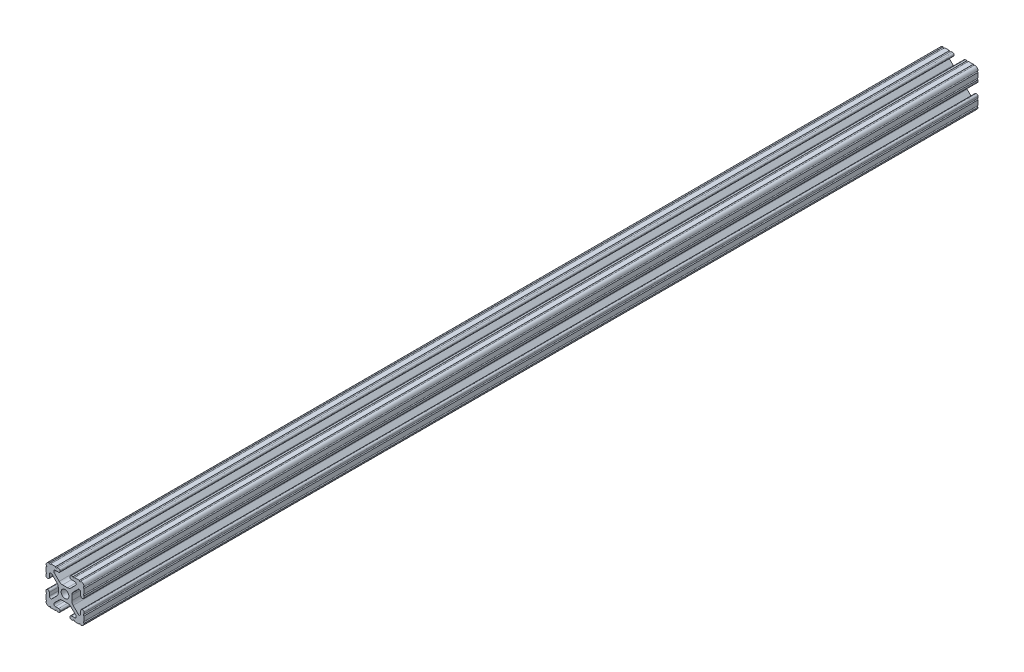
SolidWorks part; units mm, degrees
material "6061 Alloy"
ref_plane "Front" through (0, 0, 0) normal (0, 0, 1) x (1, 0, 0)
ref_plane "Top" through (0, 0, 0) normal (0, 1, 0) x (1, 0, 0)
ref_plane "Right" through (0, 0, 0) normal (1, 0, 0) x (0, 0, -1)
sketch "Sketch1" plane through (0, 0, 0) normal (0, 0, 1) x (1, 0, 0)
  line L0 (-3.2512, 12.7) -> (-3.2512, -12.7) construction
  line L1 (-12.7, -12.7) -> (12.7, -12.7) construction
  line L2 (-12.7, -12.7) -> (-12.7, 12.7) construction
  line L3 (-12.7, 12.7) -> (12.7, 12.7) construction
  line L4 (12.7, -12.7) -> (12.7, 12.7) construction
  line L5 (0, 12.7) -> (0, -12.7) construction
  line L6 (-12.7, 0) -> (12.7, 0) construction
  line L7 (3.2512, 12.7) -> (3.2512, -12.7) construction
  line L8 (-3.2512, 12.7) -> (3.2512, -12.7) construction
  circle A0 centre (0, 0) radius 2.6035
  point P0 (0, 0)
  line B0 (-7.5107, 9.4563) -> (7.5107, 9.4563) construction
  line B1 (-7.4968, -9.4098) -> (7.4968, -9.4098) construction
  line B2 (-7.1797, -8.6452) -> (-3.9523, -5.4237)
  line B3 (-1.7093, -4.4958) -> (1.7093, -4.4958)
  line B4 (3.9523, -5.4237) -> (7.1797, -8.6452)
  line B5 (6.4164, -10.4902) -> (4.2875, -10.4902)
  line B6 (3.2385, -11.5392) -> (3.2385, -11.651)
  line B7 (4.2875, -12.7) -> (5.3171, -12.7)
  line B8 (6.3331, -12.7) -> (9.5504, -12.7)
  line B9 (12.7, -9.5504) -> (12.7, -6.3331)
  line B10 (12.7, -5.3171) -> (12.7, -4.2875)
  line B11 (11.651, -3.2385) -> (11.5392, -3.2385)
  line B12 (10.4902, -4.2875) -> (10.4902, -6.4021)
  line B13 (8.7371, -7.1294) -> (5.441, -3.8408)
  line B14 (4.5085, -1.5932) -> (4.5085, 1.5932)
  line B15 (5.441, 3.8408) -> (8.7371, 7.1294)
  line B16 (10.4902, 6.4021) -> (10.4902, 4.2875)
  line B17 (11.5392, 3.2385) -> (11.651, 3.2385)
  line B18 (12.7, 4.2875) -> (12.7, 5.3171)
  line B19 (12.7, 6.3331) -> (12.7, 9.5504)
  line B20 (9.5504, 12.7) -> (6.3331, 12.7)
  line B21 (5.3171, 12.7) -> (4.2875, 12.7)
  line B22 (3.2385, 11.651) -> (3.2385, 11.5392)
  line B23 (4.2875, 10.4902) -> (6.4768, 10.4902)
  line B24 (7.207, 8.7244) -> (3.8983, 5.4232)
  line B25 (1.6558, 4.4958) -> (-1.6558, 4.4958)
  line B26 (-3.8983, 5.4232) -> (-7.207, 8.7244)
  line B27 (-6.4768, 10.4902) -> (-4.2875, 10.4902)
  line B28 (-3.2385, 11.5392) -> (-3.2385, 11.651)
  line B29 (-4.2875, 12.7) -> (-5.3171, 12.7)
  line B30 (-6.3331, 12.7) -> (-9.5504, 12.7)
  line B31 (-12.7, 9.5504) -> (-12.7, 6.3331)
  line B32 (-12.7, 5.3171) -> (-12.7, 4.2875)
  line B33 (-11.651, 3.2385) -> (-11.5392, 3.2385)
  line B34 (-10.4902, 4.2875) -> (-10.4902, 6.4021)
  line B35 (-8.7371, 7.1294) -> (-5.441, 3.8408)
  line B36 (-4.5085, 1.5932) -> (-4.5085, -1.5932)
  line B37 (-5.441, -3.8408) -> (-8.7371, -7.1294)
  line B38 (-10.4902, -6.4021) -> (-10.4902, -4.2875)
  line B39 (-11.5392, -3.2385) -> (-11.651, -3.2385)
  line B40 (-12.7, -4.2875) -> (-12.7, -5.3171)
  line B41 (-12.7, -6.3331) -> (-12.7, -9.5504)
  line B42 (-9.5504, -12.7) -> (-6.3331, -12.7)
  line B43 (-5.3171, -12.7) -> (-4.2875, -12.7)
  line B44 (-3.2385, -11.651) -> (-3.2385, -11.5392)
  line B45 (-4.2875, -10.4902) -> (-6.4164, -10.4902)
  circle B46 centre (0, 0) radius 2.6035
  arc B47 (-7.1797, -8.6452) -> (-6.4164, -10.4902) centre (-6.4164, -9.4098) ccw
  arc B48 (-1.7093, -4.4958) -> (-3.9523, -5.4237) centre (-1.7093, -7.6708) ccw
  arc B49 (3.9523, -5.4237) -> (1.7093, -4.4958) centre (1.7093, -7.6708) ccw
  arc B50 (6.4164, -10.4902) -> (7.1797, -8.6452) centre (6.4164, -9.4098) ccw
  arc B51 (4.2875, -10.4902) -> (3.2385, -11.5392) centre (4.2875, -11.5392) ccw
  arc B52 (3.2385, -11.651) -> (4.2875, -12.7) centre (4.2875, -11.651) ccw
  arc B53 (6.3331, -12.7) -> (5.3171, -12.7) centre (5.8251, -12.7) ccw
  arc B54 (10.5664, -12.6998) -> (9.5504, -12.7) centre (10.0584, -12.7) ccw
  arc B55 (10.5664, -12.6998) -> (12.6998, -10.5664) centre (10.5918, -10.5918) ccw
  arc B56 (12.7, -9.5504) -> (12.6998, -10.5664) centre (12.7, -10.0584) ccw
  arc B57 (12.7, -5.3171) -> (12.7, -6.3331) centre (12.7, -5.8251) ccw
  arc B58 (12.7, -4.2875) -> (11.651, -3.2385) centre (11.651, -4.2875) ccw
  arc B59 (11.5392, -3.2385) -> (10.4902, -4.2875) centre (11.5392, -4.2875) ccw
  arc B60 (8.7371, -7.1294) -> (10.4902, -6.4021) centre (9.4628, -6.4021) ccw
  arc B61 (4.5085, -1.5932) -> (5.441, -3.8408) centre (7.6835, -1.5932) ccw
  arc B62 (5.441, 3.8408) -> (4.5085, 1.5932) centre (7.6835, 1.5932) ccw
  arc B63 (10.4902, 6.4021) -> (8.7371, 7.1294) centre (9.4628, 6.4021) ccw
  arc B64 (10.4902, 4.2875) -> (11.5392, 3.2385) centre (11.5392, 4.2875) ccw
  arc B65 (11.651, 3.2385) -> (12.7, 4.2875) centre (11.651, 4.2875) ccw
  arc B66 (12.7, 6.3331) -> (12.7, 5.3171) centre (12.7, 5.8251) ccw
  arc B67 (12.6998, 10.5664) -> (12.7, 9.5504) centre (12.7, 10.0584) ccw
  arc B68 (12.6998, 10.5664) -> (10.5664, 12.6998) centre (10.5918, 10.5918) ccw
  arc B69 (9.5504, 12.7) -> (10.5664, 12.6998) centre (10.0584, 12.7) ccw
  arc B70 (5.3171, 12.7) -> (6.3331, 12.7) centre (5.8251, 12.7) ccw
  arc B71 (4.2875, 12.7) -> (3.2385, 11.651) centre (4.2875, 11.651) ccw
  arc B72 (3.2385, 11.5392) -> (4.2875, 10.4902) centre (4.2875, 11.5392) ccw
  arc B73 (7.207, 8.7244) -> (6.4768, 10.4902) centre (6.4768, 9.4563) ccw
  arc B74 (1.6558, 4.4958) -> (3.8983, 5.4232) centre (1.6558, 7.6708) ccw
  arc B75 (-3.8983, 5.4232) -> (-1.6558, 4.4958) centre (-1.6558, 7.6708) ccw
  arc B76 (-6.4768, 10.4902) -> (-7.207, 8.7244) centre (-6.4768, 9.4563) ccw
  arc B77 (-4.2875, 10.4902) -> (-3.2385, 11.5392) centre (-4.2875, 11.5392) ccw
  arc B78 (-3.2385, 11.651) -> (-4.2875, 12.7) centre (-4.2875, 11.651) ccw
  arc B79 (-6.3331, 12.7) -> (-5.3171, 12.7) centre (-5.8251, 12.7) ccw
  arc B80 (-10.5664, 12.6998) -> (-9.5504, 12.7) centre (-10.0584, 12.7) ccw
  arc B81 (-10.5664, 12.6998) -> (-12.6998, 10.5664) centre (-10.5918, 10.5918) ccw
  arc B82 (-12.7, 9.5504) -> (-12.6998, 10.5664) centre (-12.7, 10.0584) ccw
  arc B83 (-12.7, 5.3171) -> (-12.7, 6.3331) centre (-12.7, 5.8251) ccw
  arc B84 (-12.7, 4.2875) -> (-11.651, 3.2385) centre (-11.651, 4.2875) ccw
  arc B85 (-11.5392, 3.2385) -> (-10.4902, 4.2875) centre (-11.5392, 4.2875) ccw
  arc B86 (-8.7371, 7.1294) -> (-10.4902, 6.4021) centre (-9.4628, 6.4021) ccw
  arc B87 (-4.5085, 1.5932) -> (-5.441, 3.8408) centre (-7.6835, 1.5932) ccw
  arc B88 (-5.441, -3.8408) -> (-4.5085, -1.5932) centre (-7.6835, -1.5932) ccw
  arc B89 (-10.4902, -6.4021) -> (-8.7371, -7.1294) centre (-9.4628, -6.4021) ccw
  arc B90 (-10.4902, -4.2875) -> (-11.5392, -3.2385) centre (-11.5392, -4.2875) ccw
  arc B91 (-11.651, -3.2385) -> (-12.7, -4.2875) centre (-11.651, -4.2875) ccw
  arc B92 (-12.7, -6.3331) -> (-12.7, -5.3171) centre (-12.7, -5.8251) ccw
  arc B93 (-12.6998, -10.5664) -> (-12.7, -9.5504) centre (-12.7, -10.0584) ccw
  arc B94 (-12.6998, -10.5664) -> (-10.5664, -12.6998) centre (-10.5918, -10.5918) ccw
  arc B95 (-9.5504, -12.7) -> (-10.5664, -12.6998) centre (-10.0584, -12.7) ccw
  arc B96 (-5.3171, -12.7) -> (-6.3331, -12.7) centre (-5.8251, -12.7) ccw
  arc B97 (-4.2875, -12.7) -> (-3.2385, -11.651) centre (-4.2875, -11.651) ccw
  arc B98 (-3.2385, -11.5392) -> (-4.2875, -10.4902) centre (-4.2875, -11.5392) ccw
  dimension "Center Hole Diameter" = 5.207
  dimension "Rail Width" = 25.4
  dimension "Rail Height" = 25.4
  dimension "T-Slot Width" = 6.5024
sketch_block_instance "Block1-1"
sketch_block "Block1"
sketch "Sketch2" plane through (0, 0, 0) normal (1, 0, 0) x (0, 0, -1)
  line L0 (-298.45, 0) -> (298.45, 0) construction
  line L1 (0, 0) -> (0, 12.7) construction
  line L2 (12.7, 12.7) -> (-12.7, 12.7) construction
  line L3 (-3048, -12.7) -> (3048, -12.7) construction
  line L4 (-179.07, 0) -> (0, 12.7) construction
  line L5 (0, 12.7) -> (179.07, 0) construction
  point P5 (-179.07, 0)
  point P9 (0, 12.7)
  point P12 (179.07, 0)
  dimension "Length Range [Min]" = 25.4
  dimension "Rep Length" = 596.9
  dimension "Length Range [Max]" = 6096
  dimension "D1" = 358.14
sketch "Sketch3" plane through (0, 0, 0) normal (0, 0, 1) x (1, 0, 0)
  line L0 (-7.1797, -8.6452) -> (-3.9523, -5.4237) construction
  line L1 (-4.2875, -10.4902) -> (-6.4164, -10.4902) construction
  line L2 (-3.2385, -11.651) -> (-3.2385, -11.5392) construction
  line L3 (-5.3171, -12.7) -> (-4.2875, -12.7) construction
  line L4 (-9.5504, -12.7) -> (-6.3331, -12.7) construction
  line L5 (-12.7, -6.3331) -> (-12.7, -9.5504) construction
  line L6 (-12.7, -4.2875) -> (-12.7, -5.3171) construction
  line L7 (-11.5392, -3.2385) -> (-11.651, -3.2385) construction
  line L8 (-10.4902, -6.4021) -> (-10.4902, -4.2875) construction
  line L9 (-5.441, -3.8408) -> (-8.7371, -7.1294) construction
  line L10 (-4.5085, 1.5932) -> (-4.5085, -1.5932) construction
  line L11 (-8.7371, 7.1294) -> (-5.441, 3.8408) construction
  line L12 (-10.4902, 4.2875) -> (-10.4902, 6.4021) construction
  line L13 (-11.651, 3.2385) -> (-11.5392, 3.2385) construction
  line L14 (-12.7, 5.3171) -> (-12.7, 4.2875) construction
  line L15 (-12.7, 9.5504) -> (-12.7, 6.3331) construction
  line L16 (-6.3331, 12.7) -> (-9.5504, 12.7) construction
  line L17 (-4.2875, 12.7) -> (-5.3171, 12.7) construction
  line L18 (-3.2385, 11.5392) -> (-3.2385, 11.651) construction
  line L19 (-6.4768, 10.4902) -> (-4.2875, 10.4902) construction
  line L20 (-3.8983, 5.4232) -> (-7.207, 8.7244) construction
  line L21 (1.6558, 4.4958) -> (-1.6558, 4.4958) construction
  line L22 (7.207, 8.7244) -> (3.8983, 5.4232) construction
  line L23 (4.2875, 10.4902) -> (6.4768, 10.4902) construction
  line L24 (3.2385, 11.651) -> (3.2385, 11.5392) construction
  line L25 (5.3171, 12.7) -> (4.2875, 12.7) construction
  line L26 (9.5504, 12.7) -> (6.3331, 12.7) construction
  line L27 (12.7, 6.3331) -> (12.7, 9.5504) construction
  line L28 (12.7, 4.2875) -> (12.7, 5.3171) construction
  line L29 (11.5392, 3.2385) -> (11.651, 3.2385) construction
  line L30 (10.4902, 6.4021) -> (10.4902, 4.2875) construction
  line L31 (5.441, 3.8408) -> (8.7371, 7.1294) construction
  line L32 (4.5085, -1.5932) -> (4.5085, 1.5932) construction
  line L33 (8.7371, -7.1294) -> (5.441, -3.8408) construction
  line L34 (10.4902, -4.2875) -> (10.4902, -6.4021) construction
  line L35 (11.651, -3.2385) -> (11.5392, -3.2385) construction
  line L36 (12.7, -5.3171) -> (12.7, -4.2875) construction
  line L37 (12.7, -9.5504) -> (12.7, -6.3331) construction
  line L38 (6.3331, -12.7) -> (9.5504, -12.7) construction
  line L39 (4.2875, -12.7) -> (5.3171, -12.7) construction
  line L40 (3.2385, -11.5392) -> (3.2385, -11.651) construction
  line L41 (6.4164, -10.4902) -> (4.2875, -10.4902) construction
  line L42 (3.9523, -5.4237) -> (7.1797, -8.6452) construction
  line L43 (-1.7093, -4.4958) -> (1.7093, -4.4958) construction
  line L44 (-7.1797, -8.6452) -> (-3.9523, -5.4237)
  line L45 (-4.2875, -10.4902) -> (-6.4164, -10.4902)
  line L46 (-3.2385, -11.651) -> (-3.2385, -11.5392)
  line L47 (-5.3171, -12.7) -> (-4.2875, -12.7)
  line L48 (-9.5504, -12.7) -> (-6.3331, -12.7)
  line L49 (-12.7, -6.3331) -> (-12.7, -9.5504)
  line L50 (-12.7, -4.2875) -> (-12.7, -5.3171)
  line L51 (-11.5392, -3.2385) -> (-11.651, -3.2385)
  line L52 (-10.4902, -6.4021) -> (-10.4902, -4.2875)
  line L53 (-5.441, -3.8408) -> (-8.7371, -7.1294)
  line L54 (-4.5085, 1.5932) -> (-4.5085, -1.5932)
  line L55 (-8.7371, 7.1294) -> (-5.441, 3.8408)
  line L56 (-10.4902, 4.2875) -> (-10.4902, 6.4021)
  line L57 (-11.651, 3.2385) -> (-11.5392, 3.2385)
  line L58 (-12.7, 5.3171) -> (-12.7, 4.2875)
  line L59 (-12.7, 9.5504) -> (-12.7, 6.3331)
  line L60 (-6.3331, 12.7) -> (-9.5504, 12.7)
  line L61 (-4.2875, 12.7) -> (-5.3171, 12.7)
  line L62 (-3.2385, 11.5392) -> (-3.2385, 11.651)
  line L63 (-6.4768, 10.4902) -> (-4.2875, 10.4902)
  line L64 (-3.8983, 5.4232) -> (-7.207, 8.7244)
  line L65 (1.6558, 4.4958) -> (-1.6558, 4.4958)
  line L66 (7.207, 8.7244) -> (3.8983, 5.4232)
  line L67 (4.2875, 10.4902) -> (6.4768, 10.4902)
  line L68 (3.2385, 11.651) -> (3.2385, 11.5392)
  line L69 (5.3171, 12.7) -> (4.2875, 12.7)
  line L70 (9.5504, 12.7) -> (6.3331, 12.7)
  line L71 (12.7, 6.3331) -> (12.7, 9.5504)
  line L72 (12.7, 4.2875) -> (12.7, 5.3171)
  line L73 (11.5392, 3.2385) -> (11.651, 3.2385)
  line L74 (10.4902, 6.4021) -> (10.4902, 4.2875)
  line L75 (5.441, 3.8408) -> (8.7371, 7.1294)
  line L76 (4.5085, -1.5932) -> (4.5085, 1.5932)
  line L77 (8.7371, -7.1294) -> (5.441, -3.8408)
  line L78 (10.4902, -4.2875) -> (10.4902, -6.4021)
  line L79 (11.651, -3.2385) -> (11.5392, -3.2385)
  line L80 (12.7, -5.3171) -> (12.7, -4.2875)
  line L81 (12.7, -9.5504) -> (12.7, -6.3331)
  line L82 (6.3331, -12.7) -> (9.5504, -12.7)
  line L83 (4.2875, -12.7) -> (5.3171, -12.7)
  line L84 (3.2385, -11.5392) -> (3.2385, -11.651)
  line L85 (6.4164, -10.4902) -> (4.2875, -10.4902)
  line L86 (3.9523, -5.4237) -> (7.1797, -8.6452)
  line L87 (-1.7093, -4.4958) -> (1.7093, -4.4958)
  circle A0 centre (0, 0) radius 2.6035 construction
  circle A1 centre (0, 0) radius 2.6035
  circle A2 centre (0, 0) radius 2.6035
  arc A3 (-1.7093, -4.4958) -> (-3.9523, -5.4237) centre (-1.7093, -7.6708) ccw construction
  arc A4 (-7.1797, -8.6452) -> (-6.4164, -10.4902) centre (-6.4164, -9.4098) ccw construction
  arc A5 (-3.2385, -11.5392) -> (-4.2875, -10.4902) centre (-4.2875, -11.5392) ccw construction
  arc A6 (-4.2875, -12.7) -> (-3.2385, -11.651) centre (-4.2875, -11.651) ccw construction
  arc A7 (-5.3171, -12.7) -> (-6.3331, -12.7) centre (-5.8251, -12.7) ccw construction
  arc A8 (-9.5504, -12.7) -> (-10.5664, -12.6998) centre (-10.0584, -12.7) ccw construction
  arc A9 (-12.6998, -10.5664) -> (-10.5664, -12.6998) centre (-10.5918, -10.5918) ccw construction
  arc A10 (-12.6998, -10.5664) -> (-12.7, -9.5504) centre (-12.7, -10.0584) ccw construction
  arc A11 (-12.7, -6.3331) -> (-12.7, -5.3171) centre (-12.7, -5.8251) ccw construction
  arc A12 (-11.651, -3.2385) -> (-12.7, -4.2875) centre (-11.651, -4.2875) ccw construction
  arc A13 (-10.4902, -4.2875) -> (-11.5392, -3.2385) centre (-11.5392, -4.2875) ccw construction
  arc A14 (-10.4902, -6.4021) -> (-8.7371, -7.1294) centre (-9.4628, -6.4021) ccw construction
  arc A15 (-5.441, -3.8408) -> (-4.5085, -1.5932) centre (-7.6835, -1.5932) ccw construction
  arc A16 (-4.5085, 1.5932) -> (-5.441, 3.8408) centre (-7.6835, 1.5932) ccw construction
  arc A17 (-8.7371, 7.1294) -> (-10.4902, 6.4021) centre (-9.4628, 6.4021) ccw construction
  arc A18 (-11.5392, 3.2385) -> (-10.4902, 4.2875) centre (-11.5392, 4.2875) ccw construction
  arc A19 (-12.7, 4.2875) -> (-11.651, 3.2385) centre (-11.651, 4.2875) ccw construction
  arc A20 (-12.7, 5.3171) -> (-12.7, 6.3331) centre (-12.7, 5.8251) ccw construction
  arc A21 (-12.7, 9.5504) -> (-12.6998, 10.5664) centre (-12.7, 10.0584) ccw construction
  arc A22 (-10.5664, 12.6998) -> (-12.6998, 10.5664) centre (-10.5918, 10.5918) ccw construction
  arc A23 (-10.5664, 12.6998) -> (-9.5504, 12.7) centre (-10.0584, 12.7) ccw construction
  arc A24 (-6.3331, 12.7) -> (-5.3171, 12.7) centre (-5.8251, 12.7) ccw construction
  arc A25 (-3.2385, 11.651) -> (-4.2875, 12.7) centre (-4.2875, 11.651) ccw construction
  arc A26 (-4.2875, 10.4902) -> (-3.2385, 11.5392) centre (-4.2875, 11.5392) ccw construction
  arc A27 (-6.4768, 10.4902) -> (-7.207, 8.7244) centre (-6.4768, 9.4563) ccw construction
  arc A28 (-3.8983, 5.4232) -> (-1.6558, 4.4958) centre (-1.6558, 7.6708) ccw construction
  arc A29 (1.6558, 4.4958) -> (3.8983, 5.4232) centre (1.6558, 7.6708) ccw construction
  arc A30 (7.207, 8.7244) -> (6.4768, 10.4902) centre (6.4768, 9.4563) ccw construction
  arc A31 (3.2385, 11.5392) -> (4.2875, 10.4902) centre (4.2875, 11.5392) ccw construction
  arc A32 (4.2875, 12.7) -> (3.2385, 11.651) centre (4.2875, 11.651) ccw construction
  arc A33 (5.3171, 12.7) -> (6.3331, 12.7) centre (5.8251, 12.7) ccw construction
  arc A34 (9.5504, 12.7) -> (10.5664, 12.6998) centre (10.0584, 12.7) ccw construction
  arc A35 (12.6998, 10.5664) -> (10.5664, 12.6998) centre (10.5918, 10.5918) ccw construction
  arc A36 (12.6998, 10.5664) -> (12.7, 9.5504) centre (12.7, 10.0584) ccw construction
  arc A37 (12.7, 6.3331) -> (12.7, 5.3171) centre (12.7, 5.8251) ccw construction
  arc A38 (11.651, 3.2385) -> (12.7, 4.2875) centre (11.651, 4.2875) ccw construction
  arc A39 (10.4902, 4.2875) -> (11.5392, 3.2385) centre (11.5392, 4.2875) ccw construction
  arc A40 (10.4902, 6.4021) -> (8.7371, 7.1294) centre (9.4628, 6.4021) ccw construction
  arc A41 (5.441, 3.8408) -> (4.5085, 1.5932) centre (7.6835, 1.5932) ccw construction
  arc A42 (4.5085, -1.5932) -> (5.441, -3.8408) centre (7.6835, -1.5932) ccw construction
  arc A43 (8.7371, -7.1294) -> (10.4902, -6.4021) centre (9.4628, -6.4021) ccw construction
  arc A44 (11.5392, -3.2385) -> (10.4902, -4.2875) centre (11.5392, -4.2875) ccw construction
  arc A45 (12.7, -4.2875) -> (11.651, -3.2385) centre (11.651, -4.2875) ccw construction
  arc A46 (12.7, -5.3171) -> (12.7, -6.3331) centre (12.7, -5.8251) ccw construction
  arc A47 (12.7, -9.5504) -> (12.6998, -10.5664) centre (12.7, -10.0584) ccw construction
  arc A48 (10.5664, -12.6998) -> (12.6998, -10.5664) centre (10.5918, -10.5918) ccw construction
  arc A49 (10.5664, -12.6998) -> (9.5504, -12.7) centre (10.0584, -12.7) ccw construction
  arc A50 (6.3331, -12.7) -> (5.3171, -12.7) centre (5.8251, -12.7) ccw construction
  arc A51 (3.2385, -11.651) -> (4.2875, -12.7) centre (4.2875, -11.651) ccw construction
  arc A52 (4.2875, -10.4902) -> (3.2385, -11.5392) centre (4.2875, -11.5392) ccw construction
  arc A53 (6.4164, -10.4902) -> (7.1797, -8.6452) centre (6.4164, -9.4098) ccw construction
  arc A54 (3.9523, -5.4237) -> (1.7093, -4.4958) centre (1.7093, -7.6708) ccw construction
  circle A55 centre (0, 0) radius 2.6035
  arc A56 (-1.7093, -4.4958) -> (-3.9523, -5.4237) centre (-1.7093, -7.6708) ccw
  arc A57 (-7.1797, -8.6452) -> (-6.4164, -10.4902) centre (-6.4164, -9.4098) ccw
  arc A58 (-3.2385, -11.5392) -> (-4.2875, -10.4902) centre (-4.2875, -11.5392) ccw
  arc A59 (-4.2875, -12.7) -> (-3.2385, -11.651) centre (-4.2875, -11.651) ccw
  arc A60 (-5.3171, -12.7) -> (-6.3331, -12.7) centre (-5.8251, -12.7) ccw
  arc A61 (-9.5504, -12.7) -> (-10.5664, -12.6998) centre (-10.0584, -12.7) ccw
  arc A62 (-12.6998, -10.5664) -> (-10.5664, -12.6998) centre (-10.5918, -10.5918) ccw
  arc A63 (-12.6998, -10.5664) -> (-12.7, -9.5504) centre (-12.7, -10.0584) ccw
  arc A64 (-12.7, -6.3331) -> (-12.7, -5.3171) centre (-12.7, -5.8251) ccw
  arc A65 (-11.651, -3.2385) -> (-12.7, -4.2875) centre (-11.651, -4.2875) ccw
  arc A66 (-10.4902, -4.2875) -> (-11.5392, -3.2385) centre (-11.5392, -4.2875) ccw
  arc A67 (-10.4902, -6.4021) -> (-8.7371, -7.1294) centre (-9.4628, -6.4021) ccw
  arc A68 (-5.441, -3.8408) -> (-4.5085, -1.5932) centre (-7.6835, -1.5932) ccw
  arc A69 (-4.5085, 1.5932) -> (-5.441, 3.8408) centre (-7.6835, 1.5932) ccw
  arc A70 (-8.7371, 7.1294) -> (-10.4902, 6.4021) centre (-9.4628, 6.4021) ccw
  arc A71 (-11.5392, 3.2385) -> (-10.4902, 4.2875) centre (-11.5392, 4.2875) ccw
  arc A72 (-12.7, 4.2875) -> (-11.651, 3.2385) centre (-11.651, 4.2875) ccw
  arc A73 (-12.7, 5.3171) -> (-12.7, 6.3331) centre (-12.7, 5.8251) ccw
  arc A74 (-12.7, 9.5504) -> (-12.6998, 10.5664) centre (-12.7, 10.0584) ccw
  arc A75 (-10.5664, 12.6998) -> (-12.6998, 10.5664) centre (-10.5918, 10.5918) ccw
  arc A76 (-10.5664, 12.6998) -> (-9.5504, 12.7) centre (-10.0584, 12.7) ccw
  arc A77 (-6.3331, 12.7) -> (-5.3171, 12.7) centre (-5.8251, 12.7) ccw
  arc A78 (-3.2385, 11.651) -> (-4.2875, 12.7) centre (-4.2875, 11.651) ccw
  arc A79 (-4.2875, 10.4902) -> (-3.2385, 11.5392) centre (-4.2875, 11.5392) ccw
  arc A80 (-6.4768, 10.4902) -> (-7.207, 8.7244) centre (-6.4768, 9.4563) ccw
  arc A81 (-3.8983, 5.4232) -> (-1.6558, 4.4958) centre (-1.6558, 7.6708) ccw
  arc A82 (1.6558, 4.4958) -> (3.8983, 5.4232) centre (1.6558, 7.6708) ccw
  arc A83 (7.207, 8.7244) -> (6.4768, 10.4902) centre (6.4768, 9.4563) ccw
  arc A84 (3.2385, 11.5392) -> (4.2875, 10.4902) centre (4.2875, 11.5392) ccw
  arc A85 (4.2875, 12.7) -> (3.2385, 11.651) centre (4.2875, 11.651) ccw
  arc A86 (5.3171, 12.7) -> (6.3331, 12.7) centre (5.8251, 12.7) ccw
  arc A87 (9.5504, 12.7) -> (10.5664, 12.6998) centre (10.0584, 12.7) ccw
  arc A88 (12.6998, 10.5664) -> (10.5664, 12.6998) centre (10.5918, 10.5918) ccw
  arc A89 (12.6998, 10.5664) -> (12.7, 9.5504) centre (12.7, 10.0584) ccw
  arc A90 (12.7, 6.3331) -> (12.7, 5.3171) centre (12.7, 5.8251) ccw
  arc A91 (11.651, 3.2385) -> (12.7, 4.2875) centre (11.651, 4.2875) ccw
  arc A92 (10.4902, 4.2875) -> (11.5392, 3.2385) centre (11.5392, 4.2875) ccw
  arc A93 (10.4902, 6.4021) -> (8.7371, 7.1294) centre (9.4628, 6.4021) ccw
  arc A94 (5.441, 3.8408) -> (4.5085, 1.5932) centre (7.6835, 1.5932) ccw
  arc A95 (4.5085, -1.5932) -> (5.441, -3.8408) centre (7.6835, -1.5932) ccw
  arc A96 (8.7371, -7.1294) -> (10.4902, -6.4021) centre (9.4628, -6.4021) ccw
  arc A97 (11.5392, -3.2385) -> (10.4902, -4.2875) centre (11.5392, -4.2875) ccw
  arc A98 (12.7, -4.2875) -> (11.651, -3.2385) centre (11.651, -4.2875) ccw
  arc A99 (12.7, -5.3171) -> (12.7, -6.3331) centre (12.7, -5.8251) ccw
  arc A100 (12.7, -9.5504) -> (12.6998, -10.5664) centre (12.7, -10.0584) ccw
  arc A101 (10.5664, -12.6998) -> (12.6998, -10.5664) centre (10.5918, -10.5918) ccw
  arc A102 (10.5664, -12.6998) -> (9.5504, -12.7) centre (10.0584, -12.7) ccw
  arc A103 (6.3331, -12.7) -> (5.3171, -12.7) centre (5.8251, -12.7) ccw
  arc A104 (3.2385, -11.651) -> (4.2875, -12.7) centre (4.2875, -11.651) ccw
  arc A105 (4.2875, -10.4902) -> (3.2385, -11.5392) centre (4.2875, -11.5392) ccw
  arc A106 (6.4164, -10.4902) -> (7.1797, -8.6452) centre (6.4164, -9.4098) ccw
  arc A107 (3.9523, -5.4237) -> (1.7093, -4.4958) centre (1.7093, -7.6708) ccw
  dimension "D1" = 0
extrude "Boss-Extrude1" add sketch "Sketch3" along normal up to vertex (298.45 mm away) and the other way up to vertex (298.45 mm away) contours A56 L44 A57 L45 A58 L46 A59 L47 A60 L48 A61 A62 A63 L49 A64 L50 A65 L51 A66 L52 A67 L53 A68 L54 A69 L55 A70 L56 A71 L57 A72 L58 A73 L59 A74 A75 A76 L60 A77 L61 A78 L62 A79 L63 A80 L64 A81 L65 A82 L66 A83 L67 A84 L68 A85 L69 A86 L70 A87 A88 A89 L71 A90 L72 A91 L73 A92 L74 A93 L75 A94 L76 A95 L77 A96 L78 A97 L79 A98 L80 A99 L81 A100 A101 A102 L82 A103 L83 A104 L84 A105 L85 A106 L86 A107 L87 | A2 up to point (0, 0, 298.45) other way up to point (0, 0, -298.45)
equation "\"D1@Sketch2\"=\"Rep Length@Sketch2\"*.6"
